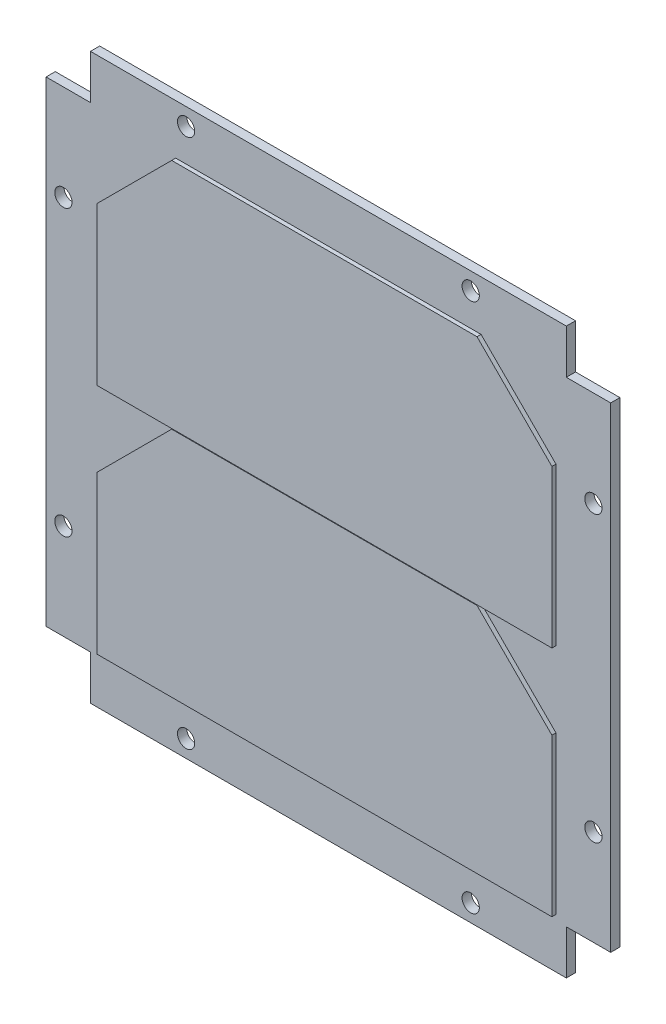
SolidWorks part; units mm, degrees
ref_plane "Front Plane" through (0, 0, 0) normal (0, 0, 1) x (1, 0, 0)
ref_plane "Top Plane" through (0, 0, 0) normal (0, 1, 0) x (1, 0, 0)
ref_plane "Right Plane" through (0, 0, 0) normal (1, 0, 0) x (0, 0, -1)
sketch "Sketch1" plane through (0, 0, 0) normal (0, 0, 1) x (1, 0, 0)
  line L0 (-65.1826, 43.8722) -> (-65.1826, 36.1722)
  line L1 (-65.1826, 36.1722) -> (-72.8826, 36.1722)
  line L2 (-72.8826, 36.1722) -> (-72.8826, -46.4278)
  line L3 (-72.8826, -46.4278) -> (-65.1826, -46.4278)
  line L4 (-65.1826, -46.4278) -> (-65.1826, -54.1278)
  line L5 (-65.1826, -54.1278) -> (17.4174, -54.1278)
  line L6 (17.4174, -54.1278) -> (17.4174, -46.4278)
  line L7 (17.4174, -46.4278) -> (25.1174, -46.4278)
  line L8 (25.1174, -46.4278) -> (25.1174, 36.1722)
  line L9 (25.1174, 36.1722) -> (17.4174, 36.1722)
  line L10 (17.4174, 36.1722) -> (17.4174, 43.8722)
  line L11 (17.4174, 43.8722) -> (-65.1826, 43.8722)
  line L12 (-63.3826, 22.2222) -> (-50.3826, 35.2222)
  line L13 (-50.3826, 35.2222) -> (2.6174, 35.2222)
  line L14 (2.6174, 35.2222) -> (15.6174, 22.2222)
  line L15 (15.6174, 22.2222) -> (15.6174, -5.0778)
  line L16 (15.6174, -5.0778) -> (-63.3826, -5.0778)
  line L17 (-63.3826, -5.0778) -> (-63.3826, 22.2222)
  line L18 (-63.3826, -18.1778) -> (-50.3826, -5.1778)
  line L19 (-50.3826, -5.1778) -> (2.6174, -5.1778)
  line L20 (2.6174, -5.1778) -> (15.6174, -18.1778)
  line L21 (15.6174, -18.1778) -> (15.6174, -45.4778)
  line L22 (15.6174, -45.4778) -> (-63.3826, -45.4778)
  line L23 (-63.3826, -18.1778) -> (-63.3826, -45.4778)
  circle A0 centre (-69.8826, 19.5722) radius 1.5
  circle A1 centre (-69.8826, -29.8278) radius 1.5
  circle A2 centre (-48.5826, -51.1278) radius 1.5
  circle A3 centre (0.8174, -51.1278) radius 1.5
  circle A4 centre (22.1174, -29.8278) radius 1.5
  circle A5 centre (22.1174, 19.5722) radius 1.5
  circle A6 centre (0.8174, 40.8722) radius 1.5
  circle A7 centre (-48.5826, 40.8722) radius 1.5
  dimension "D4" = 3
  dimension "D5" = 3
  dimension "D15" = 3
  dimension "D16" = 3
  dimension "D17" = 3
  dimension "D18" = 3
  dimension "D23" = 3
  dimension "D24" = 3
  dimension "D1" = 7.7
  dimension "D2" = 82.6
  dimension "D3" = 7.7
  dimension "D6" = 16.6
  dimension "D7" = 16.6
  dimension "D8" = 7.7
  dimension "D9" = 7.7
  dimension "D10" = 82.6
  dimension "D11" = 82.6
  dimension "D12" = 7.7
  dimension "D13" = 7.7
  dimension "D14" = 7.7
  dimension "D19" = 16.6
  dimension "D20" = 16.6
  dimension "D21" = 16.6
  dimension "D22" = 16.6
  dimension "D25" = 3
  dimension "D26" = 16.6
  dimension "D27" = 16.6
  dimension "D28" = 3
  dimension "D29" = 3
  dimension "D30" = 3
  dimension "D31" = 3
  dimension "D32" = 3
  dimension "D33" = 3
  dimension "D34" = 3
  dimension "D35" = 79
  dimension "D36" = 53
  dimension "D37" = 27.3
  dimension "D38" = 8.65
  dimension "D39" = 8.65
  dimension "D40" = 9.5
  dimension "D41" = 9.5
  dimension "D42" = 13
  dimension "D43" = 27.3
  dimension "D44" = 53
  dimension "D45" = 79
  dimension "D46" = 27.3
  dimension "D47" = 13
extrude "Boss-Extrude1" add sketch "Sketch1" along normal blind 1.6
extrude "Boss-Extrude2" add sketch "Sketch1<3>" along normal blind 2.3 contours L17 L16 L15 L14 L13 L12 | L18 L23 L22 L21 L20 L19 region at (-23.8826, 14.1855, 0) region at (-23.8826, -26.2145, 0)
sketch "Sketch1<3>" plane through (0, 0, 0) normal (0, 0, 1) x (1, 0, 0) same geometry as "Sketch1"
